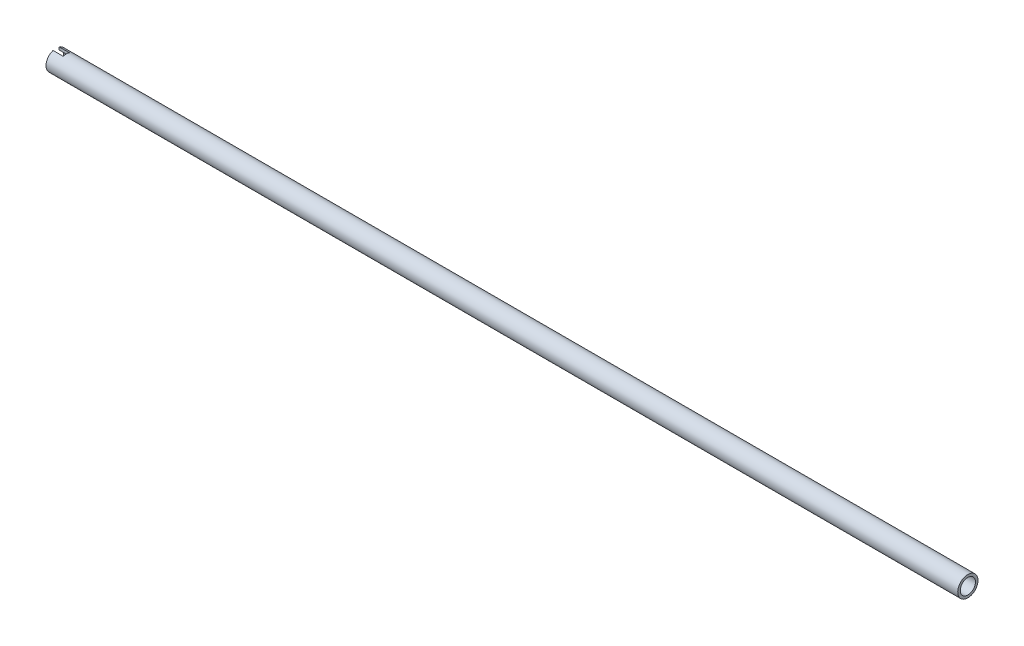
SolidWorks part; units mm, degrees
ref_plane "Front Plane" through (0, 0, 0) normal (0, 0, 1) x (1, 0, 0)
ref_plane "Top Plane" through (0, 0, 0) normal (0, 1, 0) x (1, 0, 0)
ref_plane "Right Plane" through (0, 0, 0) normal (1, 0, 0) x (0, 0, -1)
ref_axis "Axis1" through (-4.5, 0, 0) along (1, 0, 0)
sketch "Sketch1" plane through (0, 0, 0) normal (1, 0, 0) x (0, 0, -1)
  circle A0 centre (0, 0) radius 0.75
  circle A1 centre (0, 0) radius 1
  dimension "D1" = 1.5
  dimension "D2" = 2
extrude "Boss-Extrude1" add sketch "Sketch1" along normal blind 90
sketch "Sketch2" plane through (0, 0, 0) normal (-1, 0, 0) x (0, 0, 1)
  line L0 (0, 0) -> (0, 0.6106) construction
  line L2 (-0.304, 0.6106) -> (-0.304, 1.0992)
  line L3 (-0.304, 1.0992) -> (0.304, 1.0992)
  line L4 (0.304, 1.0992) -> (0.304, 0.6106)
  arc A0 (-0.304, 0.6106) -> (0.304, 0.6106) centre (0, 0.6106) ccw
  dimension "D1" = 0.608
extrude "Cut-Extrude1" cut sketch "Sketch2" against normal blind 1
equation "\"Do\"=8.5mm"
equation "\"Lo\"=10"
equation "\"screw_diam\" = 3.5mm"
equation "\"wheel_Do\"=12.5mm"
equation "\"wheel_thickness\"=4mm"
equation "\"Collet_diameter\"=4.3"
equation "\"clearance\"= 0.5mm"
equation "\"handle_body_width\" = 10mm"
equation "\"finger_diameter\"=35"
equation "\"collet_lid_diameter\"=10"
equation "\"screw_cap_diam\"=5.15"
equation "\"handle_thickness\"=12.5mm"
equation "\"post_hole_diam\"=2"
equation "\"roll_rod_diam\"= 6.5 "
equation "\"roll_rod_length\"=6.6"
equation "\"disc_diam\"=5"
equation "\"disc_width\"=1.5"
equation "\"arm_width\"=5"
equation "\"arm_thickness\"=4.5"
equation "\"wheel_total_diam\"=30"
equation "\"spring_diam\"=4.1"
equation "\"collet_length\" = 18.75mm"
equation "\"tip_length\" = 40mm"
equation "\"cable_tube_OD\"=0.508"
equation "\"D1@Sketch2\"=\"cable_tube_OD\"+0.1"
